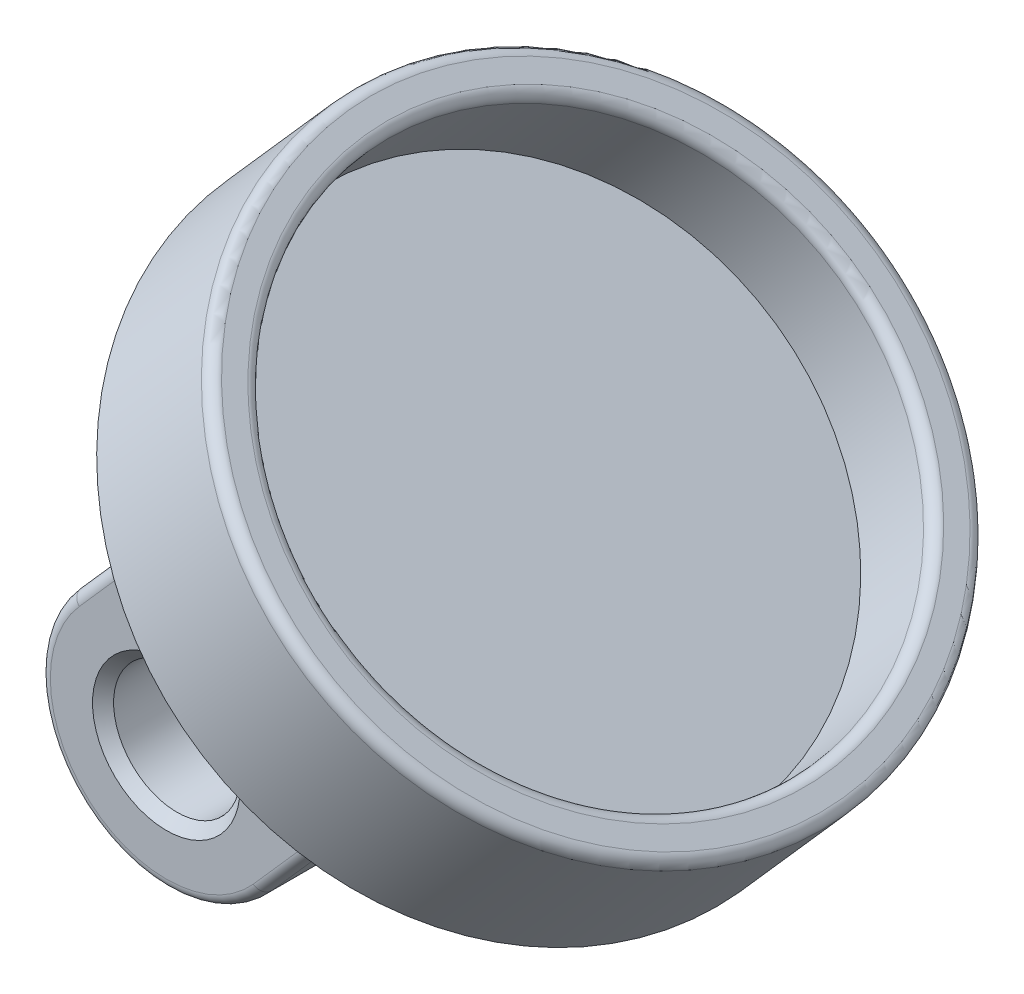
SolidWorks part; units mm, degrees
ref_plane "Front Plane" through (0, 0, 0) normal (0, 0, 1) x (1, 0, 0)
ref_plane "Top Plane" through (0, 0, 0) normal (0, 1, 0) x (1, 0, 0)
ref_plane "Right Plane" through (0, 0, 0) normal (1, 0, 0) x (0, 0, -1)
sketch "Sketch1" plane through (0, 0, 0) normal (0, 0, 1) x (1, 0, 0)
  line L1 (2.9256, 48.9181) -> (97.0713, 14.6519)
  line L2 (97.0713, 14.6519) -> (114.1723, 61.6365) construction
  line L3 (2.9256, 48.9181) -> (16.6344, 86.5828) construction
  line L4 (64.2, 56.8) -> (64.2, 145) construction
  line L5 (17.2835, 64.9758) -> (54.2, 106.8)
  line L6 (74.2, 121.8) -> (101.5245, 50.2773)
  line L7 (40.7, 148) -> (40.7, 52.5253) construction
  line L8 (87.7, 148) -> (87.7, 56.8) construction
  arc A1 (97.0713, 14.6519) -> (108.8436, 11.9213) centre (114.1723, 61.6365) ccw
  circle A2 centre (17.2835, 64.9758) radius 3
  circle A3 centre (101.5245, 50.2773) radius 3
  circle A8 centre (74.2, 121.8) radius 3
  circle A9 centre (54.2, 106.8) radius 3
  spline S1 degree 3 poles (108.8436, 11.9213) (110.0019, 11.7972) (111.159, 11.6604) (114.5227, 11.2279) (116.7249, 10.9021) (123.3121, 9.8294) (127.6782, 8.9871) (140.7169, 6.3137) (149.3307, 4.3374) (166.474, 1.206) (175.0008, 0.0515) (187.7816, -0.2014) (192.0406, -0.0398) (200.5758, 0.9156) (204.8521, 1.7093) (209.1515, 2.8921) knots 0.514918 0.514918 0.514918 0.514918 0.53125 0.53125 0.5625 0.5625 0.625 0.625 0.75 0.75 0.875 0.875 0.9375 0.9375 1 1 1 1
  point P0 (64.2, 56.8)
  point P18 (17.2835, 64.9758)
  point P19 (101.5245, 50.2773)
  point P26 (74.2, 121.8)
  point P27 (54.2, 106.8)
  point P31 (87.8622, 86.0387)
  point P32 (35.7418, 85.8879)
  dimension "D11" = 6
  dimension "D12" = 6
  dimension "D15" = 46.9165
  dimension "D17" = 6
  dimension "D18" = 6
  dimension "D3" = 20
  dimension "D4" = 35
  dimension "D5" = 8
  dimension "D6" = 10
  dimension "D7" = 8
  dimension "D8" = 10
  dimension "D9" = 65
  dimension "D10" = 50
  dimension "D13" = 37.3245
  dimension "D14" = 6.5227
  dimension "D16" = 8.1758
sketch "Sketch2" plane through (0, 0, 0) normal (0, 0, 1) x (1, 0, 0)
  line L0 (30.5124, 70.8965) -> (21.7819, 61.0053)
  line L1 (30.5124, 70.8965) -> (21.5157, 78.8375)
  line L3 (21.5157, 78.8375) -> (12.7852, 68.9463)
  line L6 (17.2835, 64.9758) -> (54.2, 106.8) construction
  circle A1 centre (17.2835, 64.9758) radius 3
  arc A2 (12.7852, 68.9463) -> (21.7819, 61.0053) centre (17.2835, 64.9758) ccw
  point P4 (21.6488, 69.9214)
  dimension "D1" = 6
  dimension "D2" = 3
  dimension "D3" = 13.193
extrude "Boss-Extrude1" add sketch "Sketch2" along normal blind 7 and the other way blind 7 contours A1 | L1 L3 A2 L0
sketch "Sketch3" plane through (48.5357, 54.988, 0) normal (0.6618, 0.7497, 0) x (0.7497, -0.6618, 0)
  circle A0 centre (-30.0399, 0) radius 14.7
  dimension "D1" = 29.4
extrude "Boss-Extrude2" add sketch "Sketch3" along normal blind 2 and the other way blind 2
sketch "Sketch4" plane through (49.8592, 56.4875, 0) normal (0.6618, 0.7497, 0) x (0.7497, -0.6618, 0)
  circle A0 centre (-30.0399, 0) radius 14.7
  circle A1 centre (-30.0399, 0) radius 12.7
  dimension "D1" = 25.4
  dimension "D2" = 2
extrude "Boss-Extrude3" add sketch "Sketch4" along normal blind 5
fillet "Fillet2" radius 0.5 2 edges at (21.1248, 88.5193, 0) (19.6253, 89.8428, 0)
fillet "Fillet4" radius 0.5 6 edges at (25.4854, 65.2012, -7) (13.313, 60.4775, -7) (16.4887, 73.1422, -7) (25.4854, 65.2012, 7) (13.313, 60.4775, 7) (16.4887, 73.1422, 7)
chamfer "Chamfer1" distance 0.5 angle 45 2 edges at (20.2835, 64.9758, 7) (20.2835, 64.9758, -7)
chamfer "Chamfer2" distance 1 angle 45 9 edges at (20.302, 77.2411, 6.8536) (20.1922, 77.338, 0) (20.302, 77.2411, -6.8536) (24.6905, 73.3675, -7) (29.0791, 69.4939, -6.8536) (29.1889, 69.397, 0) (29.0791, 69.4939, 6.8536) (24.6905, 73.3675, 7) (13.6696, 83.0953, 0)
